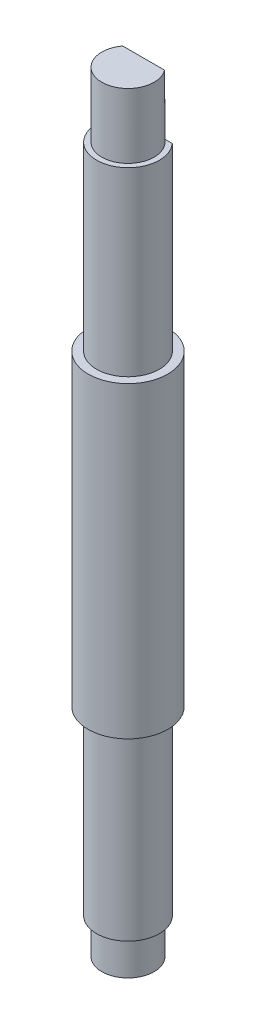
SolidWorks part; units mm, degrees
ref_plane "前视基准面" through (0, 0, 0) normal (0, 0, 1) x (1, 0, 0)
ref_plane "上视基准面" through (0, 0, 0) normal (0, 1, 0) x (1, 0, 0)
ref_plane "右视基准面" through (0, 0, 0) normal (1, 0, 0) x (0, 0, -1)
sketch "草图1" plane through (0, 0, 0) normal (0, 0, 1) x (1, 0, 0)
  line L0 (0, 5.9553) -> (0, -34.75)
  line L1 (1.25, 5.9553) -> (1.25, 2.8553)
  line L2 (1.5, 2.8553) -> (1.25, 2.8553)
  line L3 (1.5, 2.8553) -> (1.5, -5.7947)
  line L4 (1.5, -5.7947) -> (1.9, -5.7947)
  line L5 (1.9, -5.7947) -> (1.9, -20.4947)
  line L6 (1.25, -30.8447) -> (0, -30.8447)
  line L9 (1.25, 5.9553) -> (0, 5.9553)
  line L10 (1.5, -29.1447) -> (1.25, -29.1447)
  line L11 (1.25, -29.1447) -> (1.25, -30.8447)
  line L12 (1.9, -20.4947) -> (1.5, -20.4947)
  line L13 (1.5, -20.4947) -> (1.5, -29.1447)
  dimension "D2" = 1.5
  dimension "D3" = 1.25
  dimension "D4" = 3.1
  dimension "D5" = 36.8
  dimension "D6" = 1.7
  dimension "D8" = 11.75
  dimension "D9" = 10.35
  dimension "D10" = 1.25
  dimension "D11" = 1.9
revolve "旋转2" add sketch "草图1" angle 360 about L0 region at (0.8308, -12.607, 0)
ref_plane "基准面1" through (0, 3.4553, 0) normal (0, 1, 0) x (1, 0, 0)
sketch "草图5" plane through (0, 5.9553, 0) normal (0, 1, 0) x (1, 0, 0)
  line L0 (-1.118, 1) -> (1.118, 1)
  arc A0 (1.118, 1) -> (-1.118, 1) centre (0, 0) ccw
  dimension "D1" = 3
  dimension "D2" = 1
extrude "切除-拉伸3" cut sketch "草图5" against normal up to surface (11.75 mm away) up to face at (-1.9, -5.7947, 0)
sketch "草图7" plane through (0, -30.8447, 0) normal (0, -1, 0) x (1, 0, 0)
  line L0 (-1.118, -1) -> (1.118, -1) construction
  line L1 (-1.118, -1) -> (1.118, -1)
  circle A0 centre (0, 0) radius 1.5 construction
  circle A1 centre (0, 0) radius 1.5
  circle M1 centre (0, 0) radius 1.25
extrude "切除-拉伸5" cut sketch "草图7" against normal up to surface (10.35 mm away) contours L1 A1 M1 | L1 M1 region at (0, -30.8447, -1.2535) region at (0, -30.8447, -1.1009) up to face at (-1.5, -20.4947, 0)
sketch "草图8" plane through (0, -30.8447, 0) normal (0, -1, 0) x (1, 0, 0)
  circle A0 centre (0, 0) radius 0.7
  dimension "D1" = 1.4
sketch "草图10" plane through (0, 5.9553, 0) normal (0, 1, 0) x (1, 0, 0)
  line L0 (-1, 0.75) -> (1, 0.75)
  arc A0 (-0.75, 1) -> (0.75, 1) centre (0, 0) ccw construction
  arc A1 (1, 0.75) -> (-1, 0.75) centre (0, 0) ccw
  dimension "D1" = 0.75
extrude "切除-拉伸7" cut sketch "草图10" against normal blind 1.4
